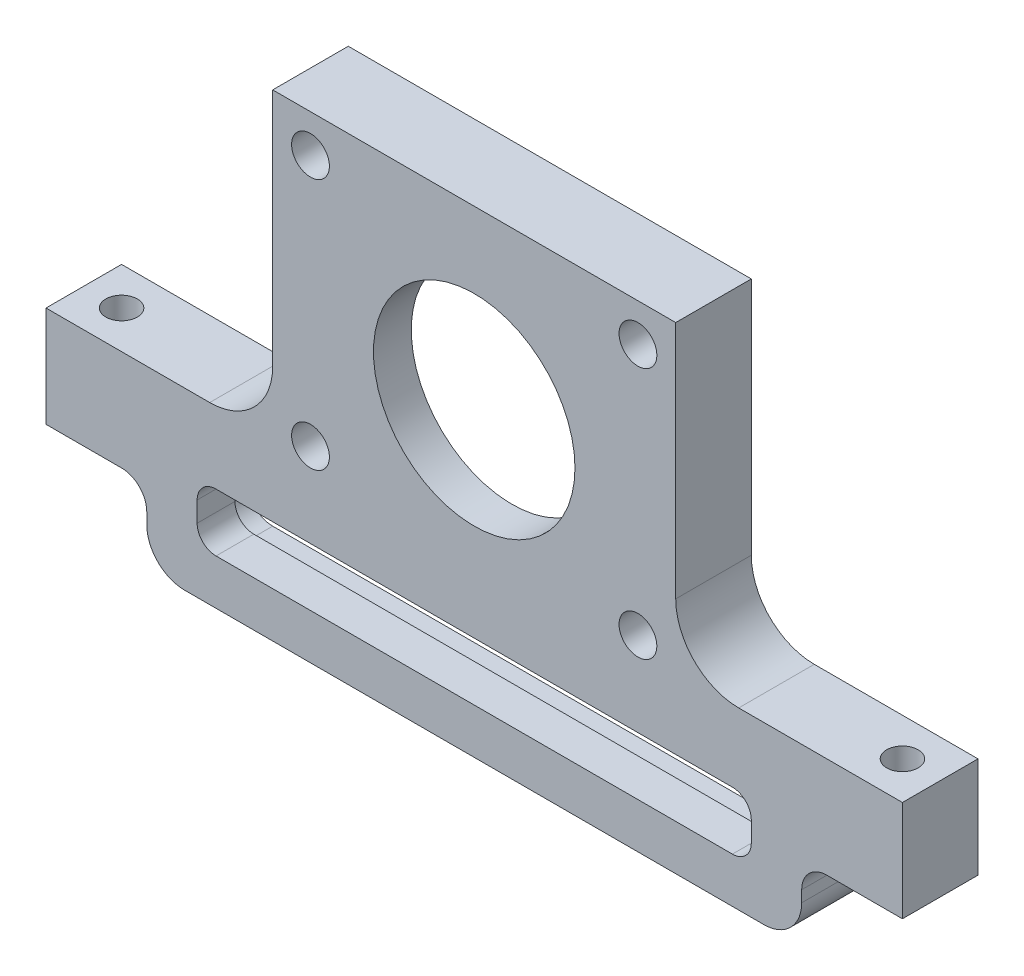
SolidWorks part; units mm, degrees
material "1060 Alloy"
ref_plane "Front Plane" through (0, 0, 0) normal (0, 0, 1) x (1, 0, 0)
ref_plane "Top Plane" through (0, 0, 0) normal (0, 1, 0) x (1, 0, 0)
ref_plane "Right Plane" through (0, 0, 0) normal (1, 0, 0) x (0, 0, -1)
sketch "Sketch1" plane through (0, 0, 0) normal (0, 0, 1) x (1, 0, 0)
  line L0 (0, 0) -> (8, 0)
  line L1 (8, 0) -> (8, -5.9)
  line L2 (8, -5.9) -> (60, -5.9)
  line L3 (60, -5.9) -> (60, 0)
  line L4 (60, 0) -> (68, 0)
  line L5 (68, 0) -> (68, 8)
  line L6 (68, 8) -> (50, 8)
  line L7 (50, 8) -> (50, 32)
  line L8 (50, 32) -> (18, 32)
  line L9 (18, 32) -> (18, 8)
  line L10 (18, 8) -> (0, 8)
  line L11 (0, 8) -> (0, 0)
  line L13 (12, 2.3) -> (56, 2.3)
  line L14 (12, 2.3) -> (12, -2.3)
  line L15 (12, -2.3) -> (56, -2.3)
  line L16 (56, 2.3) -> (56, -2.3)
  circle A0 centre (34, 18) radius 8
  dimension "D12" = 16
  dimension "D1" = 4.6
  dimension "D2" = 32
  dimension "D3" = 32
  dimension "D4" = 15.7
  dimension "D5" = 8
  dimension "D6" = 3.6
  dimension "D7" = 8
  dimension "D8" = 4
  dimension "D9" = 4
  dimension "D10" = 44
  dimension "D11" = 18
  dimension "D13" = 16
extrude "Boss-Extrude1" add sketch "Sketch1" along normal blind 6
sketch "Sketch3" plane through (0, 0, 0) normal (0, 0, -1) x (-1, 0, 0)
  circle A0 centre (-34, 18) radius 13
  dimension "D1" = 26
extrude "Cut-Extrude2" cut sketch "Sketch3" against normal offset from surface (3 mm away) 3 up to face at (34, 0, 6)
hole_wizard "Tap Drill for M3 Tap1" positions "Sketch5" profile "Sketch4" hole size "M3" standard "ISO"
sketch "Sketch5" plane through (53.9899, 0, -7.4052) normal (0, -1, 0) x (-1, 0, 0)
  line L4 (-14.0101, -13.4052) -> (-14.0101, -7.4052) construction
  line L5 (53.9899, -13.4052) -> (53.9899, -7.4052) construction
  line L7 (-6.0101, -13.4052) -> (-14.0101, -13.4052) construction
  point P0 (50.9899, -10.4052)
  point P2 (-11.0101, -10.4052)
  dimension "D1" = 3
  dimension "D2" = 3
  dimension "D3" = 3
sketch "Sketch4" plane through (3, 0, 3) normal (1, 0, 0) x (0, 0, -1)
  line L0 (0, 0) -> (0, 8.7511)
  line L1 (0, 8.7511) -> (1.25, 8)
  line L2 (1.25, 8) -> (1.25, 0)
  line L5 (1.25, 0) -> (0, 0)
  line L10 (0, 8.7511) -> (-1.25, 8) construction
  line L11 (0, -6.35) -> (0, 107.95) construction
  dimension "Hole Dia." = 2.5
  dimension "Hole Depth" = 8
  dimension "Drill Angle" = 118
sketch "Sketch7" plane through (0, 0, 0) normal (0, 0, -1) x (-1, 0, 0)
  line L1 (-58, 4) -> (-10, 4)
  line L2 (-58, 4) -> (-58, -4)
  line L3 (-58, -4) -> (-10, -4)
  line L4 (-10, 4) -> (-10, -4)
  line L5 (-56, -2.3) -> (-56, 2.3) construction
  line L6 (-56, 2.3) -> (-12, 2.3) construction
  line L9 (-12, 2.3) -> (-12, -2.3) construction
  dimension "D1" = 2
  dimension "D2" = 8
  dimension "D3" = 1.7
  dimension "D4" = 2
extrude "Cut-Extrude4" cut sketch "Sketch7" against normal blind 3
fillet "Fillet5" radius 1.5 4 edges at (12, -2.3, 4.5) (12, 2.3, 4.5) (56, 2.3, 4.5) (56, -2.3, 4.5)
fillet "Fillet1" radius 2 4 edges at (10, -4, 1.5) (10, 4, 1.5) (58, -4, 1.5) (58, 4, 1.5)
sketch "Sketch8" plane through (0, 0, 6) normal (0, 0, 1) x (1, 0, 0)
  line L0 (18, 32) -> (18, 8) construction
  line L1 (50, 32) -> (18, 32) construction
  line L3 (50, 8) -> (50, 32) construction
  circle A0 centre (21, 29) radius 1.5
  circle A1 centre (47, 29) radius 1.5
  circle A2 centre (47, 9) radius 1.5
  circle A3 centre (21, 9) radius 1.5
  dimension "D1" = 3
  dimension "D2" = 3
  dimension "D3" = 3
  dimension "D4" = 20
  dimension "D5" = 3
extrude "Cut-Extrude5" cut sketch "Sketch8" against normal up to next
fillet "Fillet2" radius 5 2 edges at (50, 8, 3) (18, 8, 3)
fillet "Fillet3" radius 2 2 edges at (60, 0, 3) (8, 0, 3)
fillet "Fillet4" radius 3 2 edges at (8, -5.9, 3) (60, -5.9, 3)
